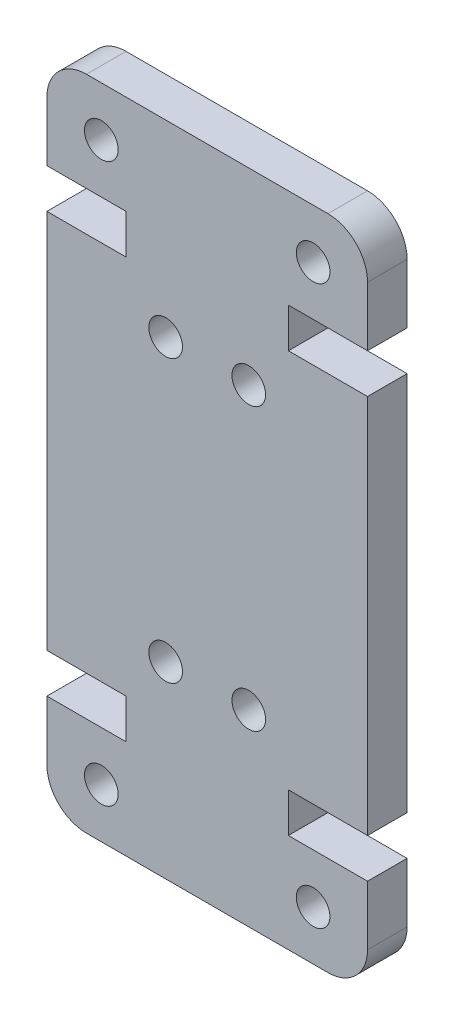
SolidWorks part; units mm, degrees
ref_plane "Front Plane" through (0, 0, 0) normal (0, 0, 1) x (1, 0, 0)
ref_plane "Top Plane" through (0, 0, 0) normal (0, 1, 0) x (1, 0, 0)
ref_plane "Right Plane" through (0, 0, 0) normal (1, 0, 0) x (0, 0, -1)
sketch "Sketch1" plane through (0, 0, 0) normal (0, 0, 1) x (1, 0, 0)
  line L0 (0, 26.21) -> (0, 7)
  line L1 (16.2, 2) -> (16.2, 5)
  line L2 (12.2, 5) -> (16.2, 5)
  line L3 (2, 0) -> (14.2, 0)
  line L4 (16.2, 7) -> (12.2, 7)
  line L5 (12.2, 7) -> (12.2, 5)
  line L6 (16.2, 26.21) -> (16.2, 7)
  line L7 (4, 7) -> (4, 5)
  line L8 (0, 31.21) -> (0, 28.21)
  line L9 (4, 28.21) -> (0, 28.21)
  line L10 (0, 7) -> (4, 7)
  line L11 (0, 26.21) -> (4, 26.21)
  line L12 (4, 5) -> (0, 5)
  line L13 (4, 26.21) -> (4, 28.21)
  line L14 (12.2, 26.21) -> (12.2, 28.21)
  line L15 (16.2, 26.21) -> (12.2, 26.21)
  line L16 (0, 2) -> (0, 5)
  line L17 (2, 33.21) -> (14.2, 33.21)
  line L18 (12.2, 28.21) -> (16.2, 28.21)
  line L19 (16.2, 31.21) -> (16.2, 28.21)
  line L20 (0, 16.605) -> (16.2, 16.605) construction
  line L21 (8.1, 33.21) -> (8.1, 0) construction
  circle A0 centre (13.45, 2.5) radius 0.85
  circle A1 centre (10.2, 9.5) radius 0.85
  arc A2 (16.2, 2) -> (14.2, 0) centre (14.2, 2) cw
  circle A3 centre (2.75, 30.71) radius 0.85
  circle A4 centre (6, 23.71) radius 0.85
  arc A5 (0, 2) -> (2, 0) centre (2, 2) ccw
  arc A6 (0, 31.21) -> (2, 33.21) centre (2, 31.21) cw
  circle A7 centre (6, 9.5) radius 0.85
  arc A8 (16.2, 31.21) -> (14.2, 33.21) centre (14.2, 31.21) ccw
  circle A9 centre (2.75, 2.5) radius 0.85
  circle A10 centre (10.2, 23.71) radius 0.85
  circle A11 centre (13.45, 30.71) radius 0.85
  point P15 (8.1, 16.605)
  dimension "D1" = 1.7
  dimension "D2" = 2
  dimension "D3" = 2.75
  dimension "D4" = 6
  dimension "D5" = 8.1
  dimension "D6" = 2.5
  dimension "D9" = 9.5
  dimension "D10" = 16.605
  dimension "D7" = 5
extrude "Boss-Extrude1" add sketch "Sketch1" along normal blind 4
sketch "Sketch2" plane through (0, 0, 0) normal (0, 0, 1) x (1, 0, 0)
  line L0 (0, 0) -> (16.2, 0)
  line L1 (16.2, 0) -> (16.2, 33.21)
  line L2 (16.2, 33.21) -> (0, 33.21)
  line L3 (0, 33.21) -> (0, 0)
extrude "Cut-Extrude2" cut sketch "Sketch2" along normal blind 2
equation "\"D5@Sketch1\"= \"fingerWidth@parametersSketch@prostheticParameters.SLDPRT\" / 2'PIP width"
equation "\"D10@Sketch1\"= ( \"HL@parametersSketch@prostheticParameters.SLDPRT\" * 0.266 - 12 - 4 ) / 2 'PIP length - Sil. sht PIP-Sil Sht MIP"
equation "\"D1@Sketch1\"= 1.5 + \"tol1@parametersSketch@prostheticParameters.SLDPRT\""
